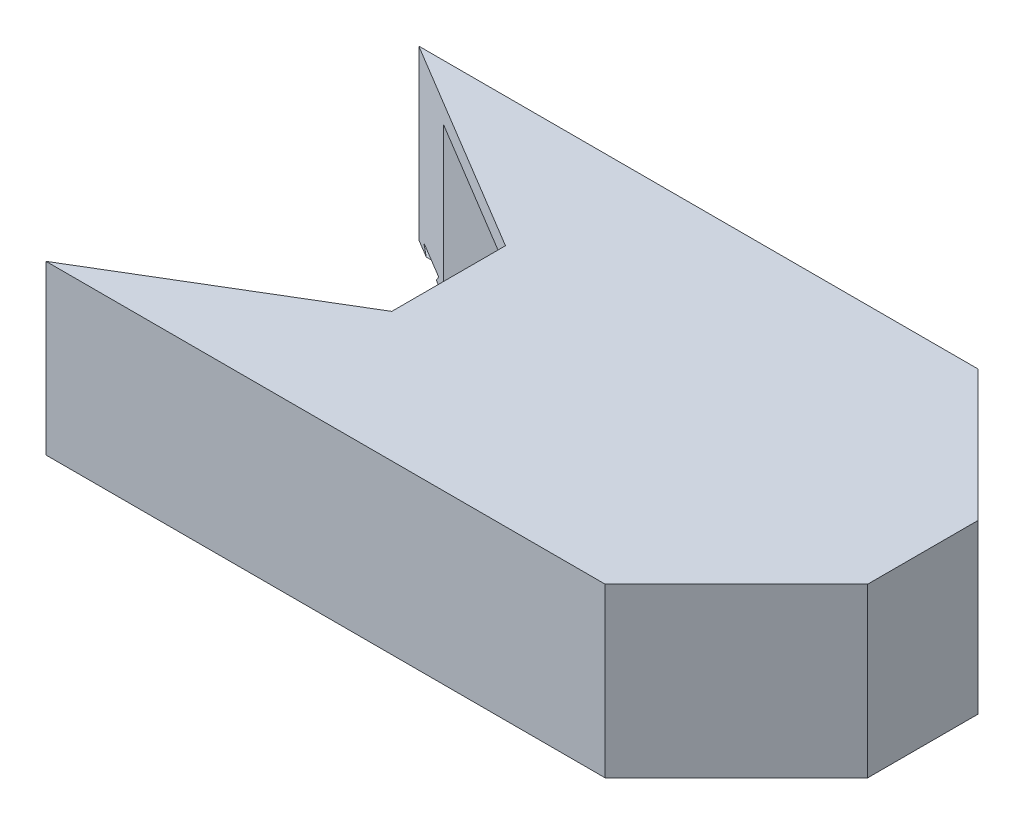
SolidWorks part; units mm, degrees
ref_plane "Front Plane" through (0, 0, 0) normal (0, 0, 1) x (1, 0, 0)
ref_plane "Top Plane" through (0, 0, 0) normal (0, 1, 0) x (1, 0, 0)
ref_plane "Right Plane" through (0, 0, 0) normal (1, 0, 0) x (0, 0, -1)
sketch "Sketch1" plane through (0, 0, 0) normal (0, 1, 0) x (1, 0, 0)
  line L0 (0, 50) -> (150, 50)
  line L1 (150, 50) -> (185.1963, 14.8037)
  line L2 (185.1963, 14.8037) -> (185.1963, -14.8037)
  line L3 (185.1963, -14.8037) -> (150, -50)
  line L4 (150, -50) -> (0, -50)
  line L5 (150, 50) -> (150, -50) construction
  line L6 (150, 0) -> (185.1963, 0) construction
  circle A0 centre (0, 0) radius 50
  dimension "D1" = 100
  dimension "D2" = 45
  dimension "D3" = 150
extrude "Boss-Extrude1" add sketch "Sketch1" against normal blind 45 contours A0 | A0 L4 L3 L2 L1 L0 region at (106.0867, 0, 0) region at (0, 0, 0)
sketch "Sketch2" plane through (0, 0, 0) normal (0, 1, 0) x (1, 0, 0)
  line L0 (0, 0) -> (0, 17.9756)
  line L1 (-0.8835, 15.9756) -> (-0.5, 17.9756) construction
  line L2 (-0.5, 17.9756) -> (0.5, 17.9756) construction
  line L3 (0, 16) -> (0, 17.9756)
  line L4 (0.8835, 15.9756) -> (0.5, 17.9756) construction
  line L5 (1.9041, 15.8863) -> (2.629, 17.7893) construction
  line L6 (2.629, 17.7893) -> (3.6138, 17.6157) construction
  line L7 (3.6442, 15.5795) -> (3.6138, 17.6157) construction
  line L8 (4.6338, 15.3143) -> (5.6782, 17.0625) construction
  line L9 (5.6782, 17.0625) -> (6.6179, 16.7205) construction
  line L10 (6.2942, 14.71) -> (6.6179, 16.7205) construction
  line L11 (7.2227, 14.277) -> (8.5548, 15.8173) construction
  line L12 (8.5548, 15.8173) -> (9.4208, 15.3173) construction
  line L13 (8.7529, 13.3935) -> (9.4208, 15.3173) construction
  line L14 (9.5921, 12.8059) -> (11.1715, 14.0915) construction
  line L15 (11.1715, 14.0915) -> (11.9375, 13.4487) construction
  line L16 (10.9457, 11.6701) -> (11.9375, 13.4487) construction
  line L17 (11.6701, 10.9457) -> (13.4487, 11.9375) construction
  line L18 (13.4487, 11.9375) -> (14.0915, 11.1715) construction
  line L19 (12.8059, 9.5921) -> (14.0915, 11.1715) construction
  line L20 (13.3935, 8.7529) -> (15.3173, 9.4208) construction
  line L21 (15.3173, 9.4208) -> (15.8173, 8.5548) construction
  line L22 (14.277, 7.2227) -> (15.8173, 8.5548) construction
  line L23 (14.71, 6.2942) -> (16.7205, 6.6179) construction
  line L24 (16.7205, 6.6179) -> (17.0625, 5.6782) construction
  line L25 (15.3143, 4.6338) -> (17.0625, 5.6782) construction
  line L26 (15.5795, 3.6442) -> (17.6157, 3.6138) construction
  line L27 (17.6157, 3.6138) -> (17.7893, 2.629) construction
  line L28 (15.8863, 1.9041) -> (17.7893, 2.629) construction
  line L29 (15.9756, 0.8835) -> (17.9756, 0.5) construction
  line L30 (17.9756, 0.5) -> (17.9756, -0.5) construction
  line L31 (15.9756, -0.8835) -> (17.9756, -0.5) construction
  line L32 (15.8863, -1.9041) -> (17.7893, -2.629) construction
  line L33 (17.7893, -2.629) -> (17.6157, -3.6138) construction
  line L34 (15.5795, -3.6442) -> (17.6157, -3.6138) construction
  line L35 (15.3143, -4.6338) -> (17.0625, -5.6782) construction
  line L36 (17.0625, -5.6782) -> (16.7205, -6.6179) construction
  line L37 (14.71, -6.2942) -> (16.7205, -6.6179) construction
  line L38 (14.277, -7.2227) -> (15.8173, -8.5548) construction
  line L39 (15.8173, -8.5548) -> (15.3173, -9.4208) construction
  line L40 (13.3935, -8.7529) -> (15.3173, -9.4208) construction
  line L41 (12.8059, -9.5921) -> (14.0915, -11.1715) construction
  line L42 (14.0915, -11.1715) -> (13.4487, -11.9375) construction
  line L43 (11.6701, -10.9457) -> (13.4487, -11.9375) construction
  line L44 (10.9457, -11.6701) -> (11.9375, -13.4487) construction
  line L45 (11.9375, -13.4487) -> (11.1715, -14.0915) construction
  line L46 (9.5921, -12.8059) -> (11.1715, -14.0915) construction
  line L47 (8.7529, -13.3935) -> (9.4208, -15.3173) construction
  line L48 (9.4208, -15.3173) -> (8.5548, -15.8173) construction
  line L49 (7.2227, -14.277) -> (8.5548, -15.8173) construction
  line L50 (6.2942, -14.71) -> (6.6179, -16.7205) construction
  line L51 (6.6179, -16.7205) -> (5.6782, -17.0625) construction
  line L52 (4.6338, -15.3143) -> (5.6782, -17.0625) construction
  line L53 (3.6442, -15.5795) -> (3.6138, -17.6157) construction
  line L54 (3.6138, -17.6157) -> (2.629, -17.7893) construction
  line L55 (1.9041, -15.8863) -> (2.629, -17.7893) construction
  line L56 (0.8835, -15.9756) -> (0.5, -17.9756) construction
  line L57 (0.5, -17.9756) -> (-0.5, -17.9756) construction
  line L58 (-0.8835, -15.9756) -> (-0.5, -17.9756) construction
  line L59 (-1.9041, -15.8863) -> (-2.629, -17.7893) construction
  line L60 (-2.629, -17.7893) -> (-3.6138, -17.6157) construction
  line L61 (-3.6442, -15.5795) -> (-3.6138, -17.6157) construction
  line L62 (-4.6338, -15.3143) -> (-5.6782, -17.0625) construction
  line L63 (-5.6782, -17.0625) -> (-6.6179, -16.7205) construction
  line L64 (-6.2942, -14.71) -> (-6.6179, -16.7205) construction
  line L65 (-7.2227, -14.277) -> (-8.5548, -15.8173) construction
  line L66 (-8.5548, -15.8173) -> (-9.4208, -15.3173) construction
  line L67 (-8.7529, -13.3935) -> (-9.4208, -15.3173) construction
  line L68 (-9.5921, -12.8059) -> (-11.1715, -14.0915) construction
  line L69 (-11.1715, -14.0915) -> (-11.9375, -13.4487) construction
  line L70 (-10.9457, -11.6701) -> (-11.9375, -13.4487) construction
  line L71 (-11.6701, -10.9457) -> (-13.4487, -11.9375) construction
  line L72 (-13.4487, -11.9375) -> (-14.0915, -11.1715) construction
  line L73 (-12.8059, -9.5921) -> (-14.0915, -11.1715) construction
  line L74 (-13.3935, -8.7529) -> (-15.3173, -9.4208) construction
  line L75 (-15.3173, -9.4208) -> (-15.8173, -8.5548) construction
  line L76 (-14.277, -7.2227) -> (-15.8173, -8.5548) construction
  line L77 (-14.71, -6.2942) -> (-16.7205, -6.6179) construction
  line L78 (-16.7205, -6.6179) -> (-17.0625, -5.6782) construction
  line L79 (-15.3143, -4.6338) -> (-17.0625, -5.6782) construction
  line L80 (-15.5795, -3.6442) -> (-17.6157, -3.6138) construction
  line L81 (-17.6157, -3.6138) -> (-17.7893, -2.629) construction
  line L82 (-15.8863, -1.9041) -> (-17.7893, -2.629) construction
  line L83 (-15.9756, -0.8835) -> (-17.9756, -0.5) construction
  line L84 (-17.9756, -0.5) -> (-17.9756, 0.5) construction
  line L85 (-15.9756, 0.8835) -> (-17.9756, 0.5) construction
  line L86 (-15.8863, 1.9041) -> (-17.7893, 2.629) construction
  line L87 (-17.7893, 2.629) -> (-17.6157, 3.6138) construction
  line L88 (-15.5795, 3.6442) -> (-17.6157, 3.6138) construction
  line L89 (-15.3143, 4.6338) -> (-17.0625, 5.6782) construction
  line L90 (-17.0625, 5.6782) -> (-16.7205, 6.6179) construction
  line L91 (-14.71, 6.2942) -> (-16.7205, 6.6179) construction
  line L92 (-14.277, 7.2227) -> (-15.8173, 8.5548) construction
  line L93 (-15.8173, 8.5548) -> (-15.3173, 9.4208) construction
  line L94 (-13.3935, 8.7529) -> (-15.3173, 9.4208) construction
  line L95 (-12.8059, 9.5921) -> (-14.0915, 11.1715) construction
  line L96 (-14.0915, 11.1715) -> (-13.4487, 11.9375) construction
  line L97 (-11.6701, 10.9457) -> (-13.4487, 11.9375) construction
  line L98 (-10.9457, 11.6701) -> (-11.9375, 13.4487) construction
  line L99 (-11.9375, 13.4487) -> (-11.1715, 14.0915) construction
  line L100 (-9.5921, 12.8059) -> (-11.1715, 14.0915) construction
  line L101 (-8.7529, 13.3935) -> (-9.4208, 15.3173) construction
  line L102 (-9.4208, 15.3173) -> (-8.5548, 15.8173) construction
  line L103 (-7.2227, 14.277) -> (-8.5548, 15.8173) construction
  line L104 (-6.2942, 14.71) -> (-6.6179, 16.7205) construction
  line L105 (-6.6179, 16.7205) -> (-5.6782, 17.0625) construction
  line L106 (-4.6338, 15.3143) -> (-5.6782, 17.0625) construction
  line L107 (-3.6442, 15.5795) -> (-3.6138, 17.6157) construction
  line L108 (-3.6138, 17.6157) -> (-2.629, 17.7893) construction
  line L109 (-1.9041, 15.8863) -> (-2.629, 17.7893) construction
  line L110 (0, 0) -> (56.068, 0) construction
  line L111 (34.5, 0) -> (33.3304, 50.2175) construction
  line L112 (34.5, 0) -> (185.1963, 0) construction
  line L114 (44.5, -10.25) -> (4.5, -10.25)
  line L115 (44.5, -10.25) -> (44.5, 10.25)
  line L116 (44.5, 10.25) -> (4.5, 10.25)
  line L117 (4.5, -10.25) -> (4.5, 10.25)
  line L118 (44.5, -10.25) -> (4.5, 10.25) construction
  line L119 (44.5, 10.25) -> (4.5, -10.25) construction
  circle A0 centre (0, 0) radius 11 construction
  circle A1 centre (0, 0) radius 16 construction
  circle A2 centre (34.5, 0) radius 16
  circle A3 centre (34.5, 0) radius 2.5
  point P10 (24.5, 0)
  point P153 (0, 0)
  dimension "D1" = 22
  dimension "D2" = 32
  dimension "D8" = 32
  dimension "D10" = 5
  dimension "D3" = 2
  dimension "D4" = 0.5
  dimension "D5" = 0.8835
  dimension "D7" = 1.0245
  dimension "D9" = 34.5
  dimension "D11" = 50.2175
  dimension "D12" = 150.6963
  dimension "D13" = 40
  dimension "D14" = 10
  dimension "D15" = 20.5
  dimension "D6" = 36
extrude "Cut-Extrude1" cut sketch "Sketch2" against normal blind 41 contours A2 L116 L117 L114 | A3 | L116 A2 L114 L115 A3 region at (31.9657, 0, 0) region at (12.1259, 0, 0) region at (34.5, 0, 0)
sketch "Sketch3" plane through (0, 0, 0) normal (0, 1, 0) x (1, 0, 0)
  line L0 (0.5, 5) -> (0.5, -5) construction
  line L1 (44.5, -10.25) -> (4.5, -10.25)
  line L2 (44.5, -10.25) -> (44.5, 10.25)
  line L3 (44.5, 10.25) -> (4.5, 10.25)
  line L4 (4.5, -10.25) -> (4.5, 10.25)
  line L5 (44.5, -10.25) -> (4.5, 10.25) construction
  line L6 (44.5, 10.25) -> (4.5, -10.25) construction
  line L7 (53, -10.25) -> (-4, -10.25)
  line L8 (53, -10.25) -> (53, 10.25)
  line L9 (53, 10.25) -> (-4, 10.25)
  line L10 (-4, -10.25) -> (-4, 10.25)
  line L11 (53, -10.25) -> (-4, 10.25) construction
  line L12 (53, 10.25) -> (-4, -10.25) construction
  line L13 (24.5, 6.4341) -> (24.5, -6.9886) construction
  line L14 (48.5, 5) -> (48.5, -5) construction
  line L15 (58, 15.25) -> (-9, 15.25)
  line L16 (-9, -15.25) -> (-9, 15.25)
  line L17 (58, -15.25) -> (-9, -15.25)
  line L18 (58, -15.25) -> (58, 15.25)
  line L19 (0, 50) -> (150, 50)
  line L20 (150, 50) -> (185.1963, 14.8037)
  line L21 (185.1963, 14.8037) -> (185.1963, -14.8037)
  line L22 (185.1963, -14.8037) -> (150, -50)
  line L23 (150, -50) -> (0, -50)
  line L24 (0, -50) -> (58, -15.25)
  line L25 (0, 50) -> (58, 15.25)
  line L26 (-9, 15.25) -> (-16.5, 28.2404) construction
  line L27 (24.5, 0) -> (-33.0818, 0) construction
  line L28 (-129.358, 0) -> (129.358, 0) construction
  circle A0 centre (0.5, 5) radius 1.5
  circle A1 centre (0.5, -5) radius 1.5
  circle A2 centre (48.5, -5) radius 1.5
  circle A3 centre (48.5, 5) radius 1.5
  arc A4 (-29, 15.8925) -> (0.5654, 32.4227) centre (-0.3957, -0.5633) cw construction
  arc A5 (0.7026, 37.1297) -> (-33.0818, 18.2407) centre (-0.3957, -0.5633) ccw
  arc A6 (0.4283, 27.7157) -> (-24.9182, 13.5443) centre (-0.3957, -0.5633) ccw
  arc A7 (0.4283, 27.7157) -> (0.7026, 37.1297) centre (0.5654, 32.4227) ccw
  arc A8 (-33.0818, 18.2407) -> (-24.9182, 13.5443) centre (-29, 15.8925) ccw
  point P0 (24.5, 0)
  point P8 (24.5, 0)
  point P42 (-16.5, 28.2404)
  point P47 (48.5, 0)
  point P53 (0, 0)
  arc M14 (0, 50) -> (0, -50) centre (0, 0) ccw
  line M20 (44.5, 10.25) -> (44.5, -10.25)
  line M21 (44.5, -10.25) -> (4.5, -10.25)
  line M22 (4.5, -10.25) -> (4.5, 10.25)
  line M23 (4.5, 10.25) -> (44.5, 10.25)
  dimension "D4" = 3
  dimension "D5" = 48
  dimension "D9" = 33
  dimension "D1" = 10
  dimension "D2" = 20.5
  dimension "D3" = 57
  dimension "D7" = 120
  dimension "D8" = 15
  dimension "D10" = 20
  dimension "D6" = 5
extrude "Cut-Extrude2" cut sketch "Sketch3" against normal blind 14 contours L10 L7 L9 A1 A0 M22 | L8 L9 L7 A2 A3 M20 region at (48.7721, 0, 0) region at (0.2279, 0, 0)
extrude "Cut-Extrude3" cut sketch "Sketch3<3>" against normal blind 19 contours A0 | A1 | A3 | A2 region at (0.5, 0, -5) region at (0.5, 0, 5) region at (48.5, 0, 5) region at (48.5, 0, -5)
sketch "Sketch3<3>" plane through (0, 0, 0) normal (0, 1, 0) x (1, 0, 0) same geometry as "Sketch3"
extrude "Cut-Extrude4" cut sketch "Sketch3<4>" against normal blind 87 contours L25 L24 L17 L16 L15 A8 A5 A7 A6 M14 | L17 L18 L15 L16 L7 L10 L9 L8 M23 M21 | L8 L9 L7 A2 A3 M20 | M20 M23 M22 M21 | L10 L7 L9 A1 A0 M22 | A0 | A1 | A5 A8 A6 A7 | A3 | A2 region at (24.5, 0, 0) region at (48.7721, 0, 0) region at (0.2279, 0, 0) region at (57.2638, 0, 0) region at (24.5, 0, -16.7219) region at (0.5, 0, -5) region at (0.5, 0, 5) region at (48.5, 0, 5) region at (48.5, 0, -5) region at (-15.471, 0, -26.3999)
sketch "Sketch3<4>" plane through (0, 0, 0) normal (0, 1, 0) x (1, 0, 0) same geometry as "Sketch3"
sketch "Sketch5" plane through (0, -45, 0) normal (0, -1, 0) x (1, 0, 0)
  line L0 (0, 50) -> (150, 50)
  line L1 (150, 50) -> (185.1963, 14.8037)
  line L2 (185.1963, 14.8037) -> (185.1963, -14.8037)
  line L3 (185.1963, -14.8037) -> (150, -50)
  line L4 (150, -50) -> (0, -50)
  line L5 (0, -50) -> (16.6906, -40)
  line L7 (16.6906, 40) -> (0, 50)
  line L9 (36.1477, 40) -> (145.8579, 40)
  line L10 (145.8579, 40) -> (175.1963, 10.6615)
  line L11 (175.1963, 10.6615) -> (175.1963, -10.6615)
  line L12 (175.1963, -10.6615) -> (145.8579, -40)
  line L13 (145.8579, -40) -> (36.1477, -40)
  line L16 (36.1477, 40) -> (1.326, 40)
  line L17 (36.1477, -40) -> (-8.7428, -40)
  line L18 (1.326, 40) -> (1.326, -40)
  line L19 (58, 15.25) -> (0, 50) construction
  line L20 (68, 20.9161) -> (36.1477, 40) construction
  line L21 (68, -20.9161) -> (68, 20.9161) construction
  line L22 (58, -15.25) -> (58, 15.25) construction
  line L23 (0, -50) -> (58, -15.25) construction
  line L24 (36.1477, -40) -> (68, -20.9161) construction
  line M1 (58, -15.25) -> (0, -50)
  line M7 (0, 50) -> (58, 15.25)
  line M8 (58, 15.25) -> (58, -15.25)
  dimension "D1" = 10
extrude "Cut-Extrude5" cut sketch "Sketch5" against normal blind 40 and the other way through all contours L17 L13 L12 L11 L10 L9 L16 M7 M8 M1 region at (104.4344, -45, 0)
ref_plane "Plane1" through (0, 0, 0) normal (-1, 0, 0) x (0, 0, 1)
sketch "Sketch6" plane through (0, 0, 0) normal (-1, 0, 0) x (0, 0, 1)
  line L0 (50, -45) -> (40, -45)
  line L1 (45, -43) -> (45, -38.8177) construction
  line L2 (43, -45) -> (42, -43)
  line L3 (42, -43) -> (48, -43)
  line L4 (47, -45) -> (48, -43)
  line L5 (40, -45) -> (40, -38.1449)
  line L6 (40, -5) -> (40, -45) construction
  line L7 (40, -38.1449) -> (50, -38.1449)
  line L8 (50, -45) -> (50, 0) construction
  line L9 (50, -38.1449) -> (50, -45)
  point P11 (45, -43)
  dimension "D1" = 3
  dimension "D3" = 2
extrude "Cut-Extrude6" cut sketch "Sketch6" against normal blind 146 contours L0 L4 L3 L2 region at (0, -43.9333, 45)
mirror "Mirror1" about plane through (0, 0, 0) normal (0, 0, 1) of "Cut-Extrude6"
